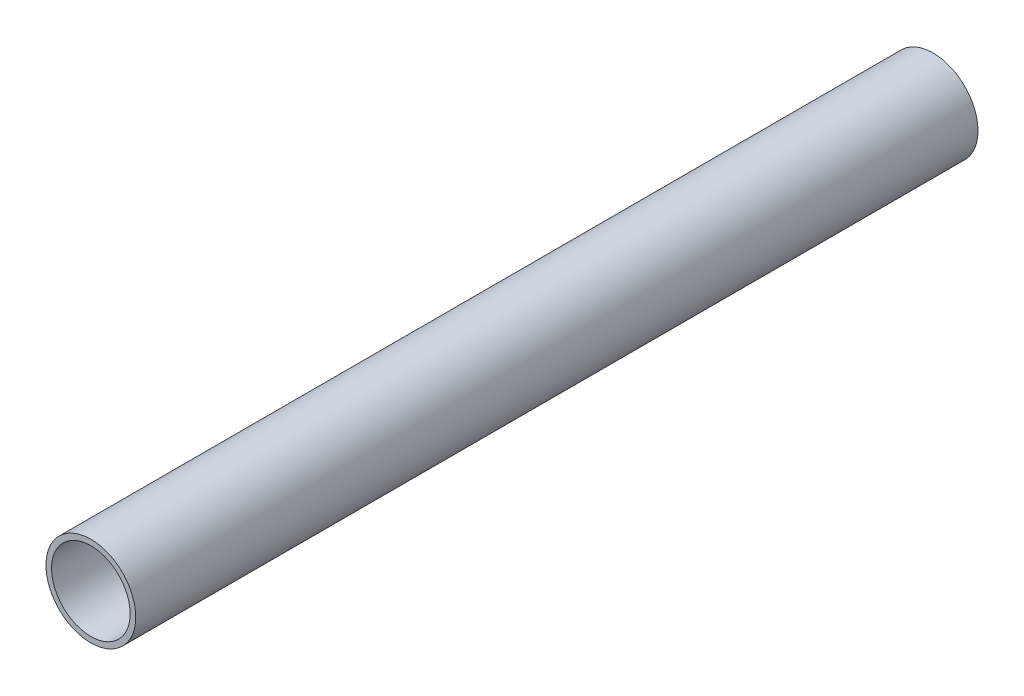
SolidWorks part; units mm, degrees
note: '?' marks a value the reader was unsure of.
ref_plane "Front Plane" through (0, 0, 0) normal (0, 0, 1) x (1, 0, 0)
ref_plane "Top Plane" through (0, 0, 0) normal (0, 1, 0) x (1, 0, 0)
ref_plane "Right Plane" through (0, 0, 0) normal (1, 0, 0) x (0, 0, -1)
sketch "Sketch1" plane through (0, 0, 0) normal (0, 0, 1) x (1, 0, 0)
  circle A0 centre (0, 0) radius 8
  circle A1 centre (0, 0) radius 7
extrude "Boss-Extrude1" add sketch "Sketch1" along normal blind 150
ref_axis "Axis1" through (0, 0, 150) along (0, 0, -1)?
